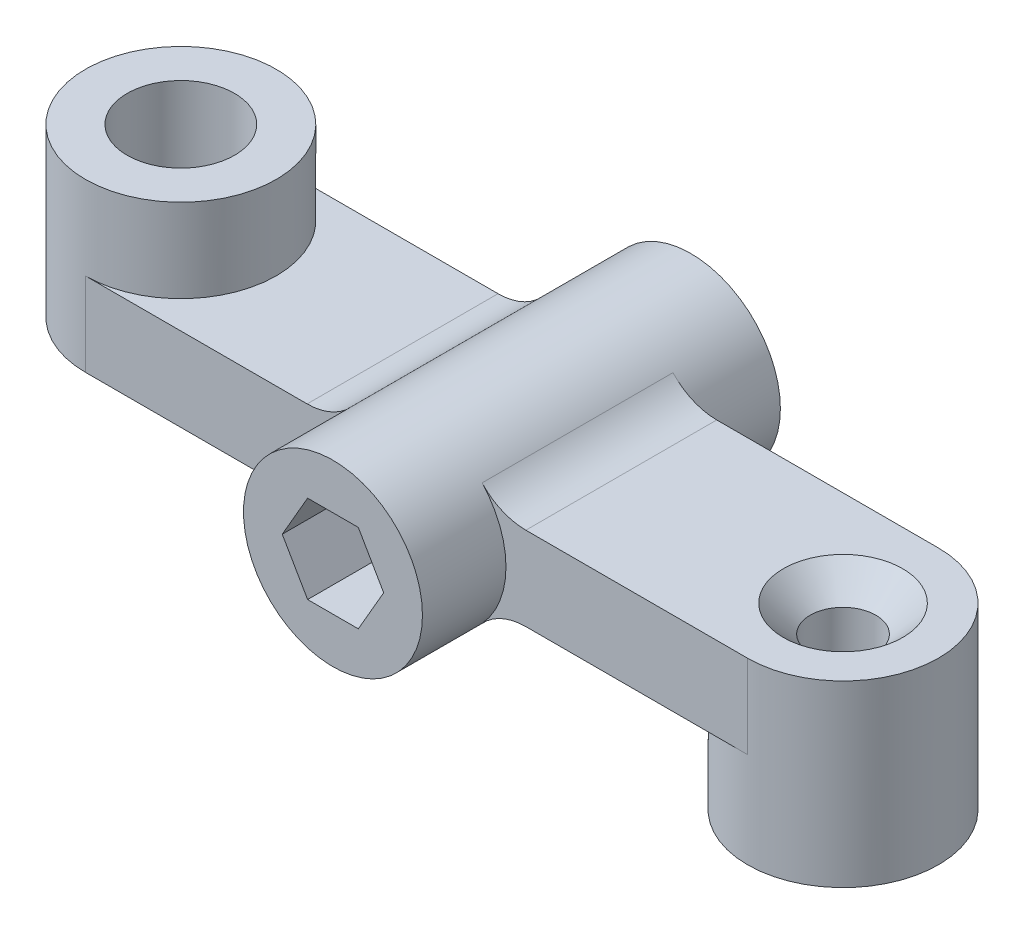
SolidWorks part; units mm, degrees
note: The reader was unsure of these and kept them because the rebuilt part matched: shared geometry of "Sketch1<3>", "Sketch1<4>", "Sketch4<3>".
material "AISI 1020 강, 냉간압연"
ref_plane "정면" through (0, 0, 0) normal (0, 0, 1) x (1, 0, 0)
ref_plane "윗면" through (0, 0, 0) normal (0, 1, 0) x (1, 0, 0)
ref_plane "우측면" through (0, 0, 0) normal (1, 0, 0) x (0, 0, -1)
sketch "Sketch1" plane through (0, 0, 0) normal (0, 1, 0) x (1, 0, 0)
  line L1 (0, 0) -> (111, 0)
  line L2 (0, 0) -> (0, 32)
  line L3 (0, 32) -> (111, 32)
  line L4 (111, 0) -> (111, 32)
  circle A0 centre (111, 16) radius 16
  circle A1 centre (0, 16) radius 16
  dimension "D2" = 32
  dimension "D1" = 111
extrude "Boss-Extrude1" add sketch "Sketch1" along normal blind 14 contours A1 L1 A0 L3 | L2 A1 | L4 A0
extrude "Boss-Extrude2" add sketch "Sketch1<3>" along normal blind 28 contours L2 A1
sketch "Sketch1<3>" plane through (0, 0, 0) normal (0, 1, 0) x (1, 0, 0) same geometry as "Sketch1"
extrude "Boss-Extrude3" add sketch "Sketch1<4>" against normal blind 16 and the other way blind 14 contours A0
sketch "Sketch1<4>" plane through (0, 0, 0) normal (0, 1, 0) x (1, 0, 0) same geometry as "Sketch1"
hole_wizard "Ø18.0 (18) Diameter Hole1" positions "3DSketch1" profile "Sketch2" hole size "Ø18.0" standard "Ansi Metric" end condition up to next
sketch3d "3DSketch1"
  line L0 (0, 14, -16) -> (0, 0, -16) construction
  point P0 (0, 28, -16)
sketch "Sketch2" plane through (0, 28, -16) normal (1, 0, 0) x (0, 0, 1)
  line L0 (0, 0) -> (0, 28)
  line L1 (0, 28) -> (9, 28)
  line L2 (9, 28) -> (9, 0)
  line L5 (9, 0) -> (0, 0)
  line L11 (0, -6.35) -> (0, 107.95) construction
  dimension "관통 구멍 지름" = 18
  dimension "관통 구멍 깊이" = 28
hole_wizard "CSK for M10 Flat Head Machine Screw1" positions "3DSketch2" profile "Sketch3" countersink size "M10" standard "Ansi Metric" end condition up to next
sketch3d "3DSketch2"
  line L0 (111, 0, -16) -> (111, -16, -16) construction
  point P0 (111, 14, -16)
sketch "Sketch3" plane through (111, 14, -16) normal (1, 0, 0) x (0, 0, 1)
  line L0 (0, 0) -> (0, 30)
  line L1 (0, 30) -> (5.5, 30)
  line L2 (5.5, 30) -> (5.5, 4.5)
  line L3 (5.5, 4.5) -> (10, 0)
  line L5 (10, 0) -> (0, 0)
  line L6 (-5.5, 4.5) -> (-10, 0) construction
  line L11 (0, -6.35) -> (0, 107.95) construction
  dimension "관통 구멍 지름" = 11
  dimension "관통 구멍 깊이" = 30
  dimension "표면 카운터싱크 지름" = 20
  dimension "표면 카운터싱크 각도" = 90
sketch "Sketch4" plane through (0, 0, 0) normal (0, 0, 1) x (1, 0, 0)
  line L0 (111, 14) -> (111, 0) construction
  line L1 (64, 7) -> (59.75, 14.3612)
  line L2 (59.75, 14.3612) -> (51.25, 14.3612)
  line L3 (51.25, 14.3612) -> (47, 7)
  line L4 (47, 7) -> (51.25, -0.3612)
  line L5 (51.25, -0.3612) -> (59.75, -0.3612)
  line L6 (59.75, -0.3612) -> (64, 7)
  circle A0 centre (55.5, 7) radius 15
  circle A1 centre (55.5, 7) radius 7.3612 construction
  point P2 (0, 0)
  point P12 (111, 7)
  line M8 (0, 0) -> (111, 0)
  line M10 (111, 14) -> (0, 14)
  dimension "D1" = 30
  dimension "D2" = 8.5
extrude "Boss-Extrude5" add sketch "Sketch4" against normal blind 46 and the other way blind 14
extrude "Cut-Extrude2" cut sketch "Sketch4<3>" against normal blind 32 contours L6 L1 L3 L4 M8 M10
sketch "Sketch4<3>" plane through (0, 0, 0) normal (0, 0, 1) x (1, 0, 0) same geometry as "Sketch4"
fillet "Fillet1" radius 10 3 edges at (68.7665, 0, -16) (42.2335, 0, -16) (68.7665, 14, -16)
